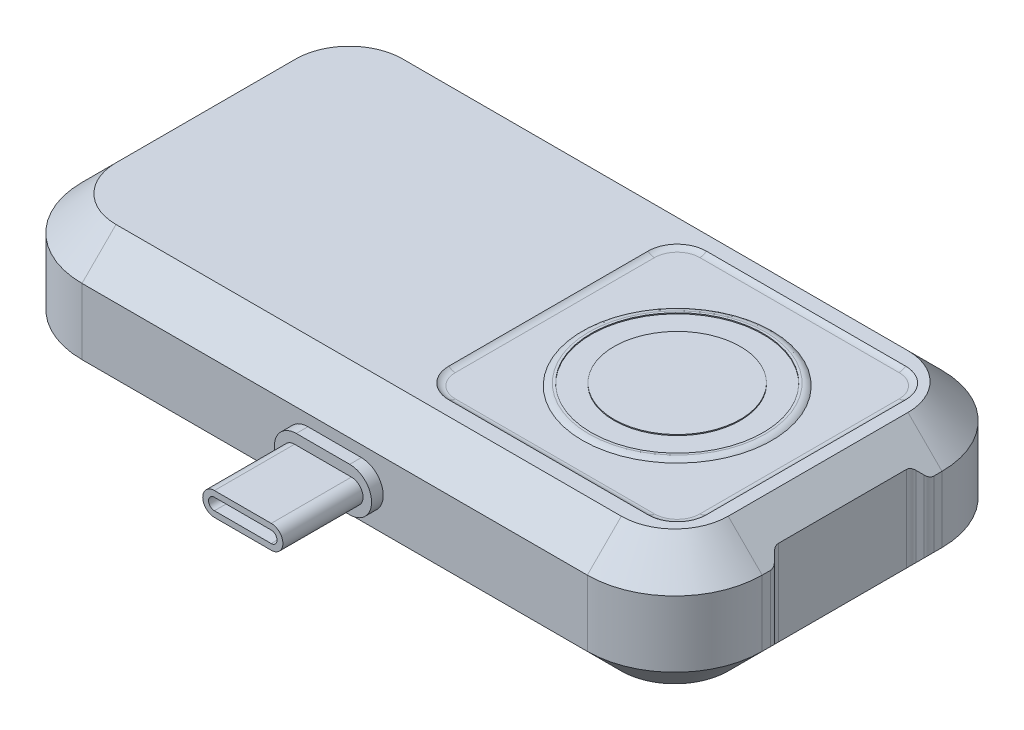
SolidWorks part; units mm, degrees
ref_plane "Front Plane" through (0, 0, 0) normal (0, 0, 1) x (1, 0, 0)
ref_plane "Top Plane" through (0, 0, 0) normal (0, 1, 0) x (1, 0, 0)
ref_plane "Right Plane" through (0, 0, 0) normal (1, 0, 0) x (0, 0, -1)
sketch "Sketch1" plane through (0, 0, 0) normal (0, 1, 0) x (1, 0, 0)
  line L1 (-35, -18.25) -> (35, -18.25)
  line L2 (-35, -18.25) -> (-35, 18.25)
  line L3 (-35, 18.25) -> (35, 18.25)
  line L4 (35, -18.25) -> (35, 18.25)
  line L5 (-35, -18.25) -> (35, 18.25) construction
  line L6 (-35, 18.25) -> (35, -18.25) construction
  point P0 (0, 0)
  dimension "D1" = 36.5
  dimension "D2" = 70
extrude "Boss-Extrude1" add sketch "Sketch1" along normal mid plane 13.8
sketch "Sketch2" plane through (0, 0, 18.25) normal (0, 0, 1) x (1, 0, 0)
  line L0 (2.75, 0) -> (-2.75, 0) construction
  line L1 (2.75, -2.25) -> (-2.75, -2.25)
  line L2 (2.75, 2.25) -> (-2.75, 2.25)
  arc A0 (2.75, -2.25) -> (2.75, 2.25) centre (2.75, 0) ccw
  arc A1 (-2.75, 2.25) -> (-2.75, -2.25) centre (-2.75, 0) ccw
  point P2 (0, 0)
  point P8 (-5, 0)
  point P9 (5, 0)
  dimension "D1" = 10
  dimension "D2" = 4.5
extrude "Boss-Extrude2" add sketch "Sketch2" along normal blind 1.2
sketch "Sketch3" plane through (0, 0, 19.45) normal (0, 0, 1) x (1, 0, 0)
  line L0 (2.925, 0) -> (-2.925, 0) construction
  line L1 (2.925, -1.2) -> (-2.925, -1.2)
  line L2 (2.925, 1.2) -> (-2.925, 1.2)
  line L3 (2.925, -0.6) -> (-2.925, -0.6)
  line L4 (2.925, 0.6) -> (-2.925, 0.6)
  arc A0 (2.925, -1.2) -> (2.925, 1.2) centre (2.925, 0) ccw
  arc A1 (-2.925, 1.2) -> (-2.925, -1.2) centre (-2.925, 0) ccw
  arc A2 (-2.925, 0.6) -> (-2.925, -0.6) centre (-2.925, 0) ccw
  arc A3 (2.925, -0.6) -> (2.925, 0.6) centre (2.925, 0) ccw
  point P2 (0, 0)
  point P8 (-4.125, 0)
  point P9 (4.125, 0)
  dimension "D1" = 2.4
  dimension "D2" = 8.25
  dimension "D3" = 0.6
extrude "Boss-Extrude3" add sketch "Sketch3" along normal blind 8.25
fillet "Fillet1" radius 9 4 edges at (35, 0, -18.25) (35, 0, 18.25) (-35, 0, -18.25) (-35, 0, 18.25)
sketch "Sketch4" plane through (0, 6.9, 0) normal (0, 1, 0) x (1, 0, 0)
  line L0 (0, 0) -> (17, 0) construction
  line L2 (27.25, 13.25) -> (6.75, 13.25)
  line L3 (30.25, 10.25) -> (30.25, -10.25)
  line L4 (27.25, -13.25) -> (6.75, -13.25)
  line L5 (3.75, 10.25) -> (3.75, -10.25)
  line L6 (30.25, 13.25) -> (3.75, -13.25) construction
  line L7 (30.25, -13.25) -> (3.75, 13.25) construction
  circle A0 centre (17, 0) radius 9.75
  arc A1 (3.75, -10.25) -> (6.75, -13.25) centre (6.75, -10.25) ccw
  arc A2 (30.25, -10.25) -> (27.25, -13.25) centre (27.25, -10.25) cw
  arc A3 (30.25, 10.25) -> (27.25, 13.25) centre (27.25, 10.25) ccw
  arc A4 (6.75, 13.25) -> (3.75, 10.25) centre (6.75, 10.25) ccw
  dimension "D2" = 3
  dimension "D1" = 26.5
  dimension "D3" = 17
extrude "Cut-Extrude1" cut sketch "Sketch4" against normal blind 0.25
sketch "Sketch5" plane through (0, 6.9, 0) normal (0, 1, 0) x (1, 0, 0)
  circle A0 centre (17, 0) radius 6.5
  circle A1 centre (17, 0) radius 8.85
  dimension "D1" = 17.7
  dimension "D2" = 13
extrude "Cut-Extrude2" cut sketch "Sketch5" against normal blind 0.1
chamfer "Chamfer1" distance 3.5 angle 45 16 edges at (0, -6.9, -18.25) (-32.364, -6.9, -15.614) (32.364, -6.9, -15.614) (-35, -6.9, 0) (35, -6.9, 0) (-32.364, -6.9, 15.614) (32.364, -6.9, 15.614) (0, -6.9, 18.25) (0, 6.9, -18.25) (-32.364, 6.9, -15.614) (32.364, 6.9, -15.614) (-35, 6.9, 0) (35, 6.9, 0) (-32.364, 6.9, 15.614) (32.364, 6.9, 15.614) (0, 6.9, 18.25)
sketch "Sketch6" plane through (0, -6.9, 0) normal (0, -1, 0) x (1, 0, 0)
  line L8 (-26, -14.25) -> (26, -14.25)
  line L9 (31, -9.25) -> (31, 9.25)
  line L10 (26, 14.25) -> (-26, 14.25)
  line L11 (-31, 9.25) -> (-31, -9.25)
  line L12 (-26, -14.25) -> (26, -14.25)
  line L13 (31, -9.25) -> (31, 9.25)
  line L14 (26, 14.25) -> (-26, 14.25)
  line L15 (-31, 9.25) -> (-31, -9.25)
  arc A8 (-31, -9.25) -> (-26, -14.25) centre (-26, -9.25) ccw
  arc A9 (26, -14.25) -> (31, -9.25) centre (26, -9.25) ccw
  arc A10 (31, 9.25) -> (26, 14.25) centre (26, 9.25) ccw
  arc A11 (-26, 14.25) -> (-31, 9.25) centre (-26, 9.25) ccw
  arc A12 (-31, -9.25) -> (-26, -14.25) centre (-26, -9.25) ccw
  arc A13 (26, -14.25) -> (31, -9.25) centre (26, -9.25) ccw
  arc A14 (31, 9.25) -> (26, 14.25) centre (26, 9.25) ccw
  arc A15 (-26, 14.25) -> (-31, 9.25) centre (-26, 9.25) ccw
  dimension "D1" = 0.5
extrude "Cut-Extrude3" cut sketch "Sketch6" against normal blind 0.2
sketch "Sketch7" plane through (0, 0, 0) normal (0, 1, 0) x (1, 0, 0)
  line L1 (-35, -9.25) -> (-35, 9.25) construction
  line L3 (-35, -9.25) -> (-35, 9.25) construction
  line L4 (-35, 0) -> (-34, 0) construction
  line L5 (0, 0) -> (0, -12.7295) construction
  line L6 (-34, -7) -> (-34, 7)
  line L7 (-34, 7) -> (-35, 8)
  line L8 (-34, -7) -> (-35, -8)
  line L9 (-35, 8) -> (-35, -8)
  line L10 (34, 7) -> (35, 8)
  line L11 (34, -7) -> (34, 7)
  line L12 (34, -7) -> (35, -8)
  line L13 (35, 8) -> (35, -8)
  point P12 (-34, 0)
  dimension "D1" = 14
  dimension "D2" = 1
  dimension "D3" = 45
extrude "Cut-Extrude4" cut sketch "Sketch7" against normal through all both and the other way through all
fillet "Fillet2" radius 1 8 edges at (-35, 0, 8) (35, 0, 8) (35, 0, -8) (-35, 0, -8) (-34, 0, 7) (34, 0, 7) (34, 0, -7) (-34, 0, -7)
fillet "Fillet3" radius 1 9 edges at (29.3713, 6.65, -12.3713) (30.25, 6.65, 0) (29.3713, 6.65, 12.3713) (17, 6.65, 13.25) (4.6287, 6.65, 12.3713) (3.75, 6.65, 0) (4.6287, 6.65, -12.3713) (17, 6.9, 9.75) (17, 6.65, -13.25)
